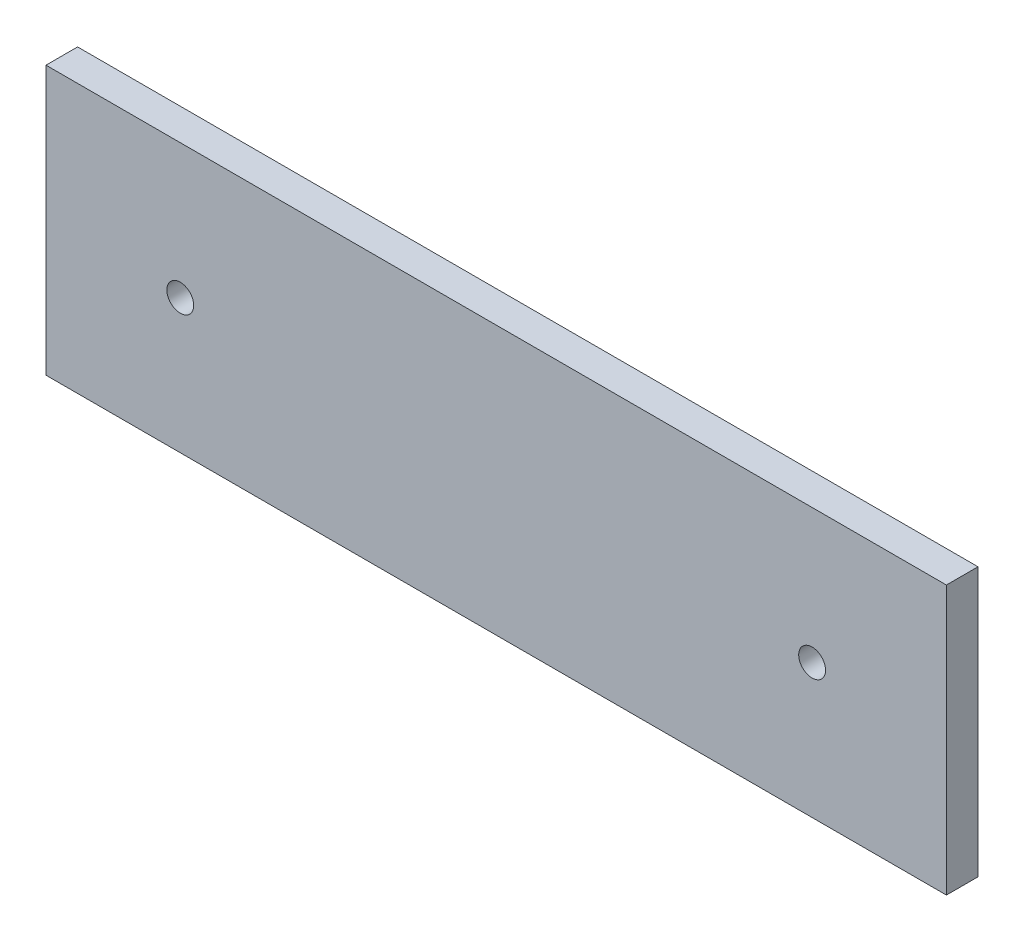
SolidWorks part; units mm, degrees
ref_plane "前视基准面" through (0, 0, 0) normal (0, 0, 1) x (1, 0, 0)
ref_plane "上视基准面" through (0, 0, 0) normal (0, 1, 0) x (1, 0, 0)
ref_plane "右视基准面" through (0, 0, 0) normal (1, 0, 0) x (0, 0, -1)
other "Configuration Table"
sketch "草图1" plane through (0, 0, 0) normal (0, 0, 1) x (1, 0, 0)
  line L1 (-17, -17) -> (97, -17)
  line L2 (-17, -17) -> (-17, 17)
  line L3 (-17, 17) -> (97, 17)
  line L4 (97, -17) -> (97, 17)
  line L5 (-17, -17) -> (97, 17) construction
  line L6 (-17, 17) -> (97, -17) construction
  circle A0 centre (0, 0) radius 1.7
  circle A1 centre (80, 0) radius 1.7
extrude "凸台-拉伸1" add sketch "草图1" along normal mid plane 4
